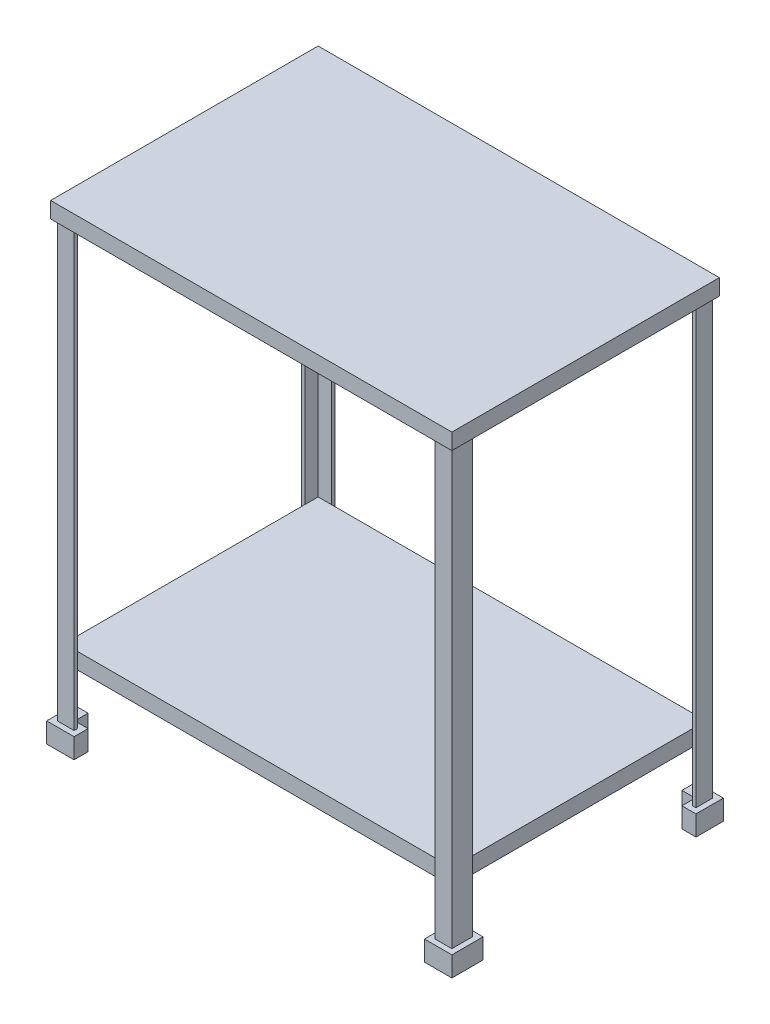
SolidWorks part; units mm, degrees
ref_plane "Alzado" through (0, 0, 0) normal (0, 0, 1) x (1, 0, 0)
ref_plane "Planta" through (0, 0, 0) normal (0, 1, 0) x (1, 0, 0)
ref_plane "Vista lateral" through (0, 0, 0) normal (1, 0, 0) x (0, 0, -1)
sketch "Croquis1" plane through (0, 0, 0) normal (0, 1, 0) x (1, 0, 0)
  line L1 (300, -200) -> (-300, -200)
  line L2 (300, -200) -> (300, 200)
  line L3 (300, 200) -> (-300, 200)
  line L4 (-300, -200) -> (-300, 200)
  line L5 (300, -200) -> (-300, 200) construction
  line L6 (300, 200) -> (-300, -200) construction
  point P0 (0, 0)
  dimension "D1" = 400
  dimension "D2" = 600
extrude "Saliente-Extruir1" add sketch "Croquis1" along normal blind 4
sketch "Croquis2" plane through (0, 0, 0) normal (0, -1, 0) x (1, 0, 0)
  line L0 (-295, 195) -> (-295, -195)
  line L1 (-295, -195) -> (295, -195)
  line L2 (295, -195) -> (295, 195)
  line L3 (295, 195) -> (-295, 195)
  line L4 (-300, 200) -> (-300, -200)
  line L5 (-300, -200) -> (300, -200)
  line L6 (300, -200) -> (300, 200)
  line L7 (300, 200) -> (-300, 200)
  line L8 (-300, 200) -> (-300, -200)
  line L9 (-300, -200) -> (300, -200)
  line L10 (300, -200) -> (300, 200)
  line L11 (300, 200) -> (-300, 200)
  dimension "D1" = 0
  dimension "D2" = 5
extrude "Saliente-Extruir2" add sketch "Croquis2" along normal blind 20
sketch "Croquis3" plane through (0, 0, 0) normal (0, -1, 0) x (1, 0, 0)
  line L0 (-270, 190) -> (-290, 190)
  line L1 (-295, 195) -> (-270, 195)
  line L2 (-295, 195) -> (-295, 170)
  line L3 (-295, 170) -> (-290, 170)
  line L4 (-270, 195) -> (-270, 190)
  line L5 (-290, 190) -> (-290, 170)
  line L6 (270, 195) -> (295, 195)
  line L7 (295, 195) -> (-295, 195) construction
  line L8 (295, 195) -> (295, 164.3409)
  line L9 (295, -195) -> (295, 195) construction
  line L10 (270, -195) -> (295, -195)
  line L11 (-295, -195) -> (295, -195) construction
  line L12 (295, -195) -> (295, -170)
  line L13 (295, -195) -> (295, 195) construction
  line L14 (-295, -170) -> (-295, -195)
  line L15 (-295, 195) -> (-295, -195) construction
  line L16 (-295, -195) -> (-270, -195)
  line L17 (-295, -195) -> (295, -195) construction
  line L18 (270, 195) -> (270, 190)
  line L19 (270, 190) -> (290, 190)
  line L20 (290, 190) -> (290, 164.3409)
  line L21 (290, 164.3409) -> (295, 164.3409)
  line L22 (-295, -170) -> (-290, -170)
  line L23 (-290, -170) -> (-290, -190)
  line L24 (-290, -190) -> (-270, -190)
  line L25 (-270, -190) -> (-270, -195)
  line L26 (295, -170) -> (290, -170)
  line L27 (290, -170) -> (290, -190)
  line L28 (290, -190) -> (270, -190)
  line L29 (270, -190) -> (270, -195)
  dimension "D1" = 5
  dimension "D2" = 5
  dimension "D3" = 25
  dimension "D4" = 25
  dimension "D5" = 25
  dimension "D6" = 25
  dimension "D7" = 25
  dimension "D8" = 30.6591
  dimension "D9" = 5
  dimension "D10" = 5
  dimension "D11" = 5
  dimension "D12" = 5
  dimension "D13" = 25
  dimension "D14" = 25
  dimension "D15" = 5
  dimension "D16" = 5
extrude "Saliente-Extruir3" add sketch "Croquis3" along normal blind 700
sketch "Croquis4" plane through (0, -700, 0) normal (0, -1, 0) x (1, 0, 0)
  line L0 (-303, 203) -> (-303, 162)
  line L1 (-303, 162) -> (-282, 162)
  line L2 (-282, 162) -> (-282, 182)
  line L3 (-282, 182) -> (-262, 182)
  line L4 (-262, 182) -> (-262, 203)
  line L5 (-262, 203) -> (-303, 203)
  line L6 (-295, 195) -> (-295, 170)
  line L7 (-295, 170) -> (-290, 170)
  line L8 (-290, 170) -> (-290, 190)
  line L9 (-290, 190) -> (-270, 190)
  line L10 (-270, 190) -> (-270, 195)
  line L11 (-270, 195) -> (-295, 195)
  line L12 (-295, 195) -> (-295, 170)
  line L13 (-295, 170) -> (-290, 170)
  line L14 (-290, 170) -> (-290, 190)
  line L15 (-290, 190) -> (-270, 190)
  line L16 (-270, 190) -> (-270, 195)
  line L17 (-270, 195) -> (-295, 195)
  line L18 (-282, -162) -> (-303, -162)
  line L19 (-303, -162) -> (-303, -203)
  line L20 (-303, -203) -> (-262, -203)
  line L21 (-262, -203) -> (-262, -182)
  line L22 (-262, -182) -> (-282, -182)
  line L23 (-282, -182) -> (-282, -162)
  line L24 (-290, -170) -> (-295, -170)
  line L25 (-295, -170) -> (-295, -195)
  line L26 (-295, -195) -> (-270, -195)
  line L27 (-270, -195) -> (-270, -190)
  line L28 (-270, -190) -> (-290, -190)
  line L29 (-290, -190) -> (-290, -170)
  line L30 (-290, -170) -> (-295, -170)
  line L31 (-295, -170) -> (-295, -195)
  line L32 (-295, -195) -> (-270, -195)
  line L33 (-270, -195) -> (-270, -190)
  line L34 (-270, -190) -> (-290, -190)
  line L35 (-290, -190) -> (-290, -170)
  line L36 (262, 203) -> (262, 182)
  line L37 (262, 182) -> (282, 182)
  line L38 (282, 182) -> (282, 156.3409)
  line L39 (282, 156.3409) -> (303, 156.3409)
  line L40 (303, 156.3409) -> (303, 203)
  line L41 (303, 203) -> (262, 203)
  line L42 (270, 195) -> (270, 190)
  line L43 (270, 190) -> (290, 190)
  line L44 (290, 190) -> (290, 164.3409)
  line L45 (290, 164.3409) -> (295, 164.3409)
  line L46 (295, 164.3409) -> (295, 195)
  line L47 (295, 195) -> (270, 195)
  line L48 (270, 195) -> (270, 190)
  line L49 (270, 190) -> (290, 190)
  line L50 (290, 190) -> (290, 164.3409)
  line L51 (290, 164.3409) -> (295, 164.3409)
  line L52 (295, 164.3409) -> (295, 195)
  line L53 (295, 195) -> (270, 195)
  line L54 (262, -182) -> (262, -203)
  line L55 (262, -203) -> (303, -203)
  line L56 (303, -203) -> (303, -162)
  line L57 (303, -162) -> (282, -162)
  line L58 (282, -162) -> (282, -182)
  line L59 (282, -182) -> (262, -182)
  line L60 (270, -190) -> (270, -195)
  line L61 (270, -195) -> (295, -195)
  line L62 (295, -195) -> (295, -170)
  line L63 (295, -170) -> (290, -170)
  line L64 (290, -170) -> (290, -190)
  line L65 (290, -190) -> (270, -190)
  line L66 (270, -190) -> (270, -195)
  line L67 (270, -195) -> (295, -195)
  line L68 (295, -195) -> (295, -170)
  line L69 (295, -170) -> (290, -170)
  line L70 (290, -170) -> (290, -190)
  line L71 (290, -190) -> (270, -190)
  dimension "D1" = 0
  dimension "D2" = 8
  dimension "D3" = 0
  dimension "D4" = 8
  dimension "D5" = 0
  dimension "D6" = 8
  dimension "D7" = 0
  dimension "D8" = 8
extrude "Saliente-Extruir4" add sketch "Croquis4" against normal blind 30
sketch "Croquis5" plane through (0, 0, -190) normal (0, 0, 1) x (1, 0, 0)
  line L0 (-290, -670) -> (-290, 0) construction
  line L9 (290, -670) -> (290, 0) construction
  line L10 (-290, -570) -> (290, -570)
  line L11 (-290, -570) -> (-290, -594)
  line L12 (-290, -594) -> (290, -594)
  line L13 (290, -570) -> (290, -594)
  line L14 (300, -20) -> (-300, -20) construction
  dimension "D1" = 550
  dimension "D3" = 24
extrude "Saliente-Extruir5" add sketch "Croquis5" along direction (0, 0, 1) on the side of the normal up to surface (380 mm away) up to face at (-280, -335, 190)
sketch "Croquis7" plane through (0, -594, 0) normal (0, -1, 0) x (1, 0, 0)
  line L24 (-270, 185) -> (-285, 185)
  line L25 (-285, 185) -> (-285, 170)
  line L26 (-285, 170) -> (-285, -170)
  line L27 (-285, -170) -> (-285, -185)
  line L28 (-285, -185) -> (-270, -185)
  line L29 (-270, -185) -> (270, -185)
  line L30 (270, -185) -> (285, -185)
  line L31 (285, -185) -> (285, -170)
  line L32 (285, -170) -> (285, 164.3409)
  line L33 (285, 164.3409) -> (285, 185)
  line L34 (285, 185) -> (270, 185)
  line L35 (270, 185) -> (-270, 185)
  line L36 (-270, 185) -> (-285, 185)
  line L37 (-285, 185) -> (-285, 170)
  line L38 (-285, 170) -> (-285, -170)
  line L39 (-285, -170) -> (-285, -185)
  line L40 (-285, -185) -> (-270, -185)
  line L41 (-270, -185) -> (270, -185)
  line L42 (270, -185) -> (285, -185)
  line L43 (285, -185) -> (285, -170)
  line L44 (285, -170) -> (285, 164.3409)
  line L45 (285, 164.3409) -> (285, 185)
  line L46 (285, 185) -> (270, 185)
  line L47 (270, 185) -> (-270, 185)
  dimension "D1" = 5
extrude "Cortar-Extruir2" cut sketch "Croquis7" against normal blind 18
